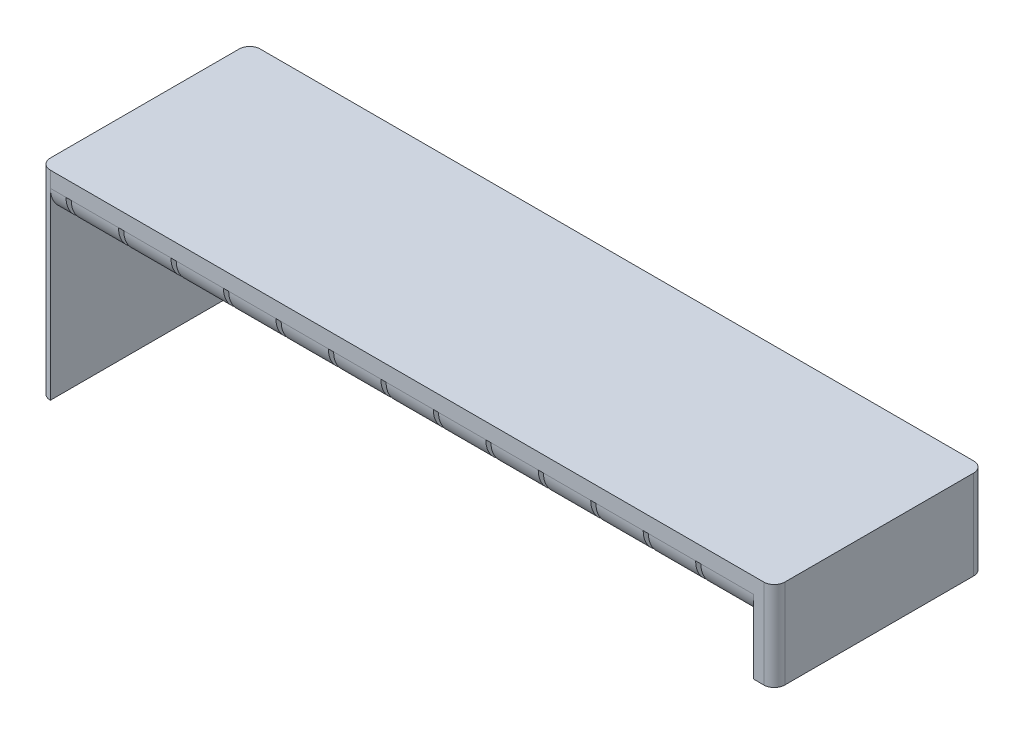
SolidWorks part; units mm, degrees
ref_plane "Front Plane" through (0, 0, 0) normal (0, 0, 1) x (1, 0, 0)
ref_plane "Top Plane" through (0, 0, 0) normal (0, 1, 0) x (1, 0, 0)
ref_plane "Right Plane" through (0, 0, 0) normal (1, 0, 0) x (0, 0, -1)
sketch "Sketch1" plane through (0, 0, 0) normal (0, 1, 0) x (1, 0, 0)
  line L1 (-70, 20) -> (70, 20)
  line L2 (-70, 20) -> (-70, -20)
  line L3 (-70, -20) -> (70, -20)
  line L4 (70, 20) -> (70, -20)
  line L5 (-70, 20) -> (70, -20) construction
  line L6 (-70, -20) -> (70, 20) construction
  line L7 (-70, 20) -> (-68, 20)
  line L8 (-70, 20) -> (-70, -20)
  line L9 (-70, -20) -> (-68, -20)
  line L10 (-68, 20) -> (-68, -20)
  line L11 (-70, 20) -> (-68, -20) construction
  line L12 (-70, -20) -> (-68, 20) construction
  line L13 (70, 20) -> (68, 20)
  line L14 (70, 20) -> (70, -20)
  line L15 (70, -20) -> (68, -20)
  line L16 (68, 20) -> (68, -20)
  line L17 (70, 20) -> (68, -20) construction
  line L18 (70, -20) -> (68, 20) construction
  point P0 (0, 0)
  point P8 (-69, 0)
  point P11 (69, 0)
  dimension "D1" = 140
  dimension "D2" = 40
  dimension "D3" = 2
  dimension "D4" = 2
extrude "Boss-Extrude1" add sketch "Sketch1" along normal blind 8 contours L16 L1 L10 L3 | L1 L16 L3 L4 | L10 L1 L2 L3 region at (-69, 0, 0) region at (0, 0, 0) region at (69, 0, 0)
extrude "Boss-Extrude2" add sketch "Sketch1<3>" against normal blind 9 contours L1 L16 L3 L4 region at (69, 0, 0)
sketch "Sketch1<3>" plane through (0, 0, 0) normal (0, 1, 0) x (1, 0, 0) same geometry as "Sketch1"
sketch "Sketch2" plane through (68, 0, 0) normal (-1, 0, 0) x (0, 0, 1)
  line L0 (-20, 0) -> (20, 0) construction
  line L1 (9.125, 0) -> (-9.125, 0)
  line L2 (9.125, 0) -> (9.125, -9)
  line L3 (9.125, -9) -> (-9.125, -9)
  line L4 (-9.125, 0) -> (-9.125, -9)
  line L5 (9.125, 0) -> (-9.125, -9) construction
  line L6 (9.125, -9) -> (-9.125, 0) construction
  line L7 (-20, -9) -> (-20, 0) construction
  line L8 (9.125, -9) -> (8.525, -9)
  line L9 (9.125, -9) -> (9.125, 0)
  line L10 (9.125, 0) -> (8.525, 0)
  line L11 (8.525, -9) -> (8.525, 0)
  line L12 (9.125, -9) -> (8.525, 0) construction
  line L13 (9.125, 0) -> (8.525, -9) construction
  line L14 (-9.125, -9) -> (-8.525, -9)
  line L15 (-9.125, -9) -> (-9.125, 0)
  line L16 (-9.125, 0) -> (-8.525, 0)
  line L17 (-8.525, -9) -> (-8.525, 0)
  line L18 (-9.125, -9) -> (-8.525, 0) construction
  line L19 (-9.125, 0) -> (-8.525, -9) construction
  line L20 (8.525, -0.6) -> (-8.525, -0.6)
  line L21 (8.525, -0.6) -> (8.525, 0)
  line L22 (8.525, 0) -> (-8.525, 0)
  line L23 (-8.525, -0.6) -> (-8.525, 0)
  line L24 (8.525, -0.6) -> (-8.525, 0) construction
  line L25 (8.525, 0) -> (-8.525, -0.6) construction
  line L26 (-9.125, -9) -> (-20, -9)
  line L27 (-9.125, -9) -> (-9.125, 0)
  line L28 (-9.125, 0) -> (-20, 0)
  line L29 (-20, -9) -> (-20, 0)
  line L30 (-9.125, -9) -> (-20, 0) construction
  line L31 (-9.125, 0) -> (-20, -9) construction
  line L33 (9.125, -9) -> (20, -9)
  line L34 (9.125, -9) -> (9.125, 0)
  line L35 (9.125, 0) -> (20, 0)
  line L36 (20, -9) -> (20, 0)
  line L37 (9.125, -9) -> (20, 0) construction
  line L38 (9.125, 0) -> (20, -9) construction
  point P4 (0, -4.5)
  point P7 (0, 0)
  point P11 (8.825, -4.5)
  point P14 (-8.825, -4.5)
  point P18 (0, -0.3)
  point P20 (-14.5625, -4.5)
  point P25 (14.5625, -4.5)
  line M3 (20, 0) -> (-20, 0)
  line M4 (-20, 0) -> (-20, -9)
  line M6 (20, -9) -> (20, 0)
  dimension "D1" = 18.25
  dimension "D2" = 9
  dimension "D3" = 0.6
  dimension "D4" = 0.6
  dimension "D5" = 0.6
extrude "Boss-Extrude3" add sketch "Sketch2" along normal blind 1 contours L2 L33 M6 M3 | L26 L4 M3 M4 region at (68, -4.5, 14.5625) region at (68, -4.5, -14.5625)
extrude "Boss-Extrude4" add sketch "Sketch2<3>" along normal blind 1 from surface contours L11 L3 L2 M3 | L2 L33 M6 M3 | L20 L11 L1 L17 | L3 L17 L4 M3 | L26 L4 M3 M4 region at (68, -4.5, 8.825) region at (68, -4.5, 14.5625) region at (68, -0.3, 0) region at (68, -4.5, -8.825) region at (68, -4.5, -14.5625) starting at face at (67, -4.5, 14.5625)
sketch "Sketch2<3>" plane through (68, 0, 0) normal (-1, 0, 0) x (0, 0, 1) same geometry as "Sketch2"
ref_plane "Plane1" through (64, 0, 0) normal (-1, 0, 0) x (0, 0, 1)
extrude "Boss-Extrude5" add sketch "Sketch1<4>" against normal blind 30 contours L10 L1 L2 L3 region at (-69, 0, 0)
sketch "Sketch1<4>" plane through (0, 0, 0) normal (0, 1, 0) x (1, 0, 0) same geometry as "Sketch1"
sketch "Sketch3" plane through (64, 0, 0) normal (-1, 0, 0) x (0, 0, 1)
  line L0 (0, 0) -> (0, -6.5) construction
  line L1 (11.6554, -3.25) -> (-11.6554, -3.25)
  line L2 (-11.6554, -3.25) -> (-11.6554, 0)
  line L3 (-11.6554, 0) -> (0, 0)
  line L4 (0, 0) -> (11.6554, 0)
  line L5 (-20, 0) -> (20, 0) construction
  line L6 (11.6554, 0) -> (11.6554, -3.25)
  circle A0 centre (0, -6.5) radius 12.1
  point P7 (0, -3.25)
  dimension "D1" = 24.2
  dimension "D2" = 6.5
extrude "Cut-Extrude1" cut sketch "Sketch3" along normal up to surface (132 mm away) contours L1 A0 | L4 L0 L1 A0 | L0 L3 A0 L1 | L4 A0 L3 region at (64, -1.6604, 5.5213) region at (64, -1.6604, -5.5213) region at (64, 2.2914, 0) region at (64, -9.9308, 0) up to face at (-68, -15, 0)
fillet "Fillet1" radius 5 2 edges at (-1, 0, 20) (-1, 0, -20)
fillet "Fillet2" radius 2 4 edges at (-70, -11, 20) (-70, -11, -20) (70, -0.5, 20) (70, -0.5, -20)
extrude "Boss-Extrude6" add sketch "Sketch3<3>" along normal up to surface and the other way up to surface contours A0 L3 L2 | A0 L6 L4 region at (64, -1.0038, 11.2018) region at (64, -1.0038, -11.2018) up to face at (-68, -5.8089, 0) other way up to face at (66, -2.9271, 0)
sketch "Sketch3<3>" plane through (64, 0, 0) normal (-1, 0, 0) x (0, 0, 1) same geometry as "Sketch3"
fillet "Fillet3" radius 0.5 2 edges at (-1, -3.25, -11.6554) (-1, -3.25, 11.6554)
fillet "Fillet5" radius 1 1 edges at (64, 0, 0)
ref_plane "sensor plane" through (66, 0, 0) normal (-1, 0, 0) x (0, 0, 1)
ref_plane "S1" through (56, 0, 0) normal (-1, 0, 0) x (0, 0, 1)
sketch "Sketch4" plane through (56, 0, 0) normal (-1, 0, 0) x (0, 0, 1)
  line L0 (20, 5) -> (20, -9) construction
  line L1 (-20, 5) -> (20, 5)
  line L2 (-20, 5) -> (-20, -5)
  line L3 (-20, -5) -> (20, -5)
  line L4 (20, 5) -> (20, -5)
  line L5 (-20, 5) -> (20, -5) construction
  line L6 (-20, -5) -> (20, 5) construction
  line L7 (-18, 8) -> (18, 8) construction
  point P0 (0, 0)
  point P7 (20, -9)
  point P8 (0, 0)
  point P10 (20, 3.8844)
  dimension "D1" = 3
extrude "Cut-Extrude2" cut sketch "Sketch4" along normal blind 1 contours L3 L4 L1 L2
pattern_linear "LPattern1" count 13 spacing 10 along (-1, 0, 0) of "Cut-Extrude2"
